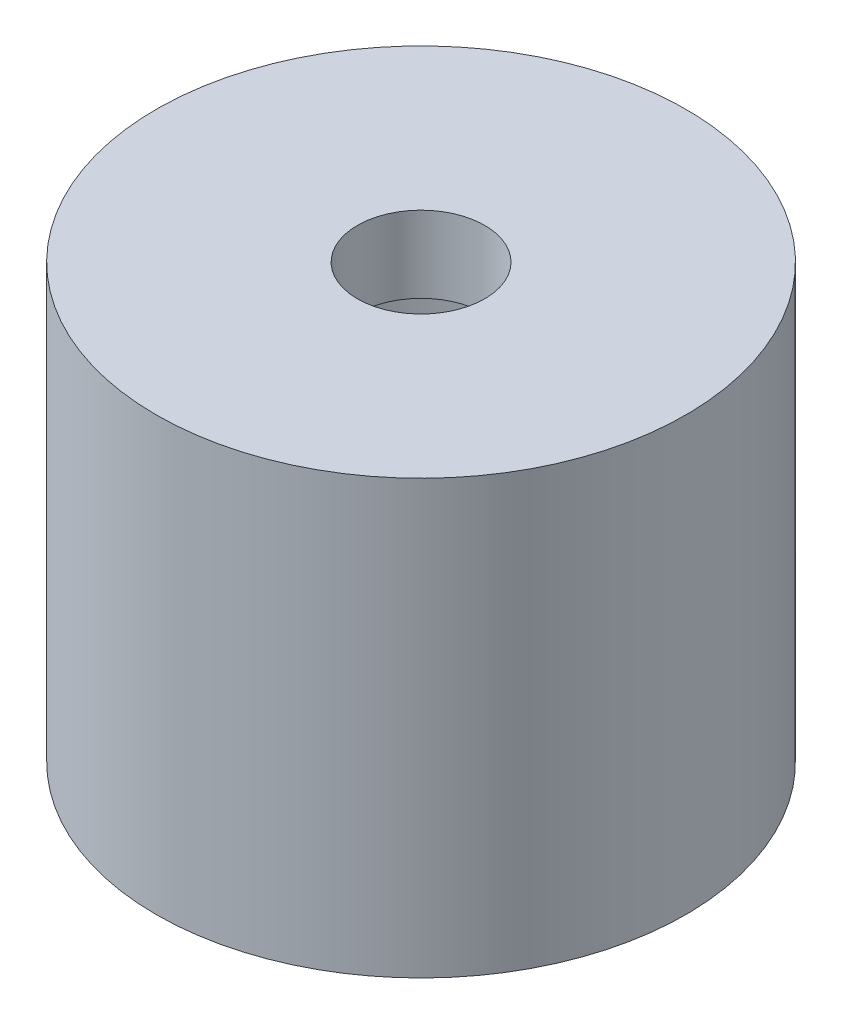
SolidWorks part; units mm, degrees
ref_plane "Front Plane" through (0, 0, 0) normal (0, 0, 1) x (1, 0, 0)
ref_plane "Top Plane" through (0, 0, 0) normal (0, 1, 0) x (1, 0, 0)
ref_plane "Right Plane" through (0, 0, 0) normal (1, 0, 0) x (0, 0, -1)
sketch "Sketch1" plane through (0, 0, 0) normal (0, 1, 0) x (1, 0, 0)
  circle A0 centre (0, 0) radius 13.97
  circle A2 centre (0, 0) radius 16.51
  dimension "D1" = 27.94
  dimension "D2" = 2.54
extrude "Boss-Extrude1" add sketch "Sketch1" against normal blind 22.225
extrude "Boss-Extrude2" add sketch "Sketch1<2>" along normal blind 4.7625 contours A2
sketch "Sketch1<2>" plane through (0, 0, 0) normal (0, 1, 0) x (1, 0, 0) same geometry as "Sketch1"
hole_wizard "5/16 (0.3125) Diameter Hole1" positions "Sketch8" profile "Sketch9" hole size "5/16" standard "ANSI Inch" end condition up to next
sketch "Sketch8" plane through (0, 4.7625, 0) normal (0, 1, 0) x (1, 0, 0)
  point P0 (0, 0)
sketch "Sketch9" plane through (0, 4.7625, 0) normal (1, 0, 0) x (0, 0, 1)
  line L0 (0, 0) -> (0, 4.7625)
  line L1 (0, 4.7625) -> (3.9687, 4.7625)
  line L2 (3.9687, 4.7625) -> (3.9688, 0)
  line L5 (3.9688, 0) -> (0, 0)
  line L11 (0, -6.35) -> (0, 107.95) construction
  dimension "Thru Hole Dia." = 7.9375
  dimension "Thru Hole Depth" = 4.7625
